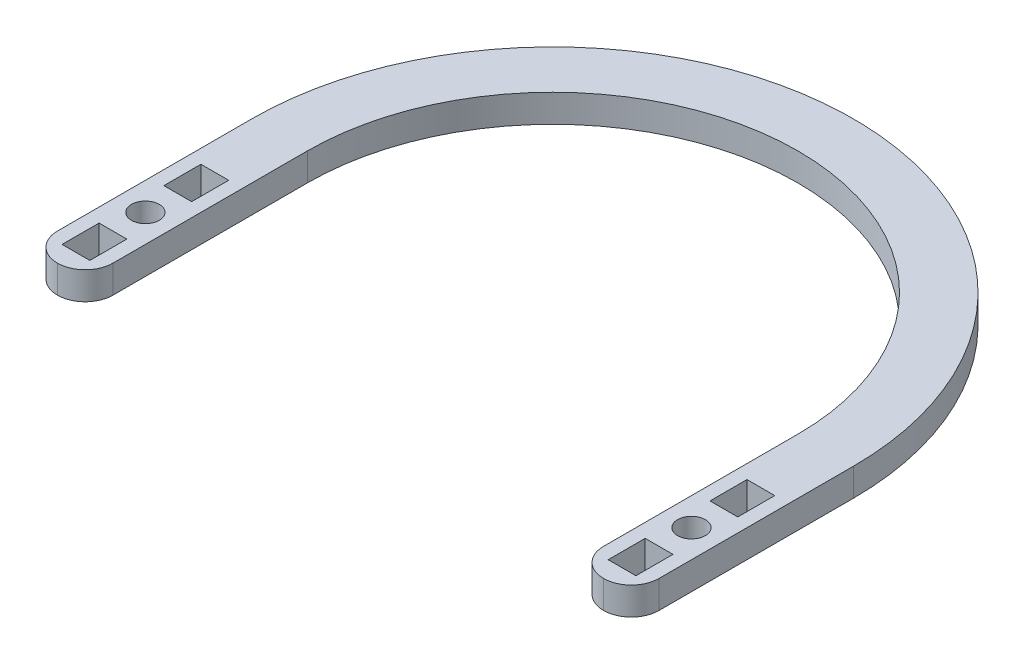
SolidWorks part; units mm, degrees
material "Lasercut ABS"
ref_plane "Front Plane" through (0, 0, 0) normal (0, 0, 1) x (1, 0, 0)
ref_plane "Top Plane" through (0, 0, 0) normal (0, 1, 0) x (1, 0, 0)
ref_plane "Right Plane" through (0, 0, 0) normal (1, 0, 0) x (0, 0, -1)
sketch "Sketch1" plane through (0, 0, 0) normal (0, 1, 0) x (1, 0, 0)
  line L0 (-29.5, -9) -> (-29.5, -20) construction
  line L1 (-32.5, 0) -> (-32.5, -24)
  line L2 (-31, -7) -> (-28, -7)
  line L3 (-31, -7) -> (-31, -11)
  line L4 (-31, -11) -> (-28, -11)
  line L5 (-28, -7) -> (-28, -11)
  line L6 (-31, -7) -> (-28, -11) construction
  line L7 (-31, -11) -> (-28, -7) construction
  line L8 (-31, -18) -> (-28, -18)
  line L9 (-31, -18) -> (-31, -22)
  line L10 (-31, -22) -> (-28, -22)
  line L11 (-28, -18) -> (-28, -22)
  line L12 (-31, -18) -> (-28, -22) construction
  line L13 (-31, -22) -> (-28, -18) construction
  line L14 (-32.5, -24) -> (-26.5, -24)
  line L15 (-26.5, -24) -> (-26.5, 0)
  line L16 (26.5, 0) -> (26.5, -24)
  line L17 (26.5, -24) -> (32.5, -24)
  line L18 (32.5, -24) -> (32.5, 0)
  line L19 (0, 0) -> (0, -23.7709) construction
  line L20 (31, -11) -> (28, -11)
  line L21 (31, -7) -> (31, -11)
  line L22 (31, -7) -> (28, -7)
  line L23 (28, -7) -> (28, -11)
  line L24 (31, -22) -> (28, -22)
  line L25 (31, -18) -> (31, -22)
  line L26 (31, -18) -> (28, -18)
  line L27 (28, -18) -> (28, -22)
  circle A0 centre (-29.5, -14.5) radius 1.5
  arc A1 (-26.5, 0) -> (26.5, 0) centre (0, 0) cw
  arc A2 (-32.5, 0) -> (32.5, 0) centre (0, 0) cw
  circle A3 centre (29.5, -14.5) radius 1.5
  dimension "D1" = 3
  dimension "D2" = 3
  dimension "D3" = 4
  dimension "D4" = 7
  dimension "D5" = 6
  dimension "D6" = 3
  dimension "D7" = 2
  dimension "D8" = 59
  dimension "D9" = 24
extrude "Boss-Extrude1" add sketch "Sketch1" along normal blind 3
fillet "Fillet1" radius 3 4 edges at (32.5, 1.5, 24) (26.5, 1.5, 24) (-26.5, 1.5, 24) (-32.5, 1.5, 24)
sketch "Sketch2" plane through (0, 3, 0) normal (0, 1, 0) x (1, 0, 0)
  arc A0 (-12.5, 25.0549) -> (12.5, 25.0549) centre (0, 0) cw construction
  arc A1 (32.5, 0) -> (-32.5, 0) centre (0, 0) ccw construction
  text T0 "E7 ONO V2" font "1CamBam_Stick_3" height 2.5
  dimension "D1" = 28
  dimension "D2" = 25
